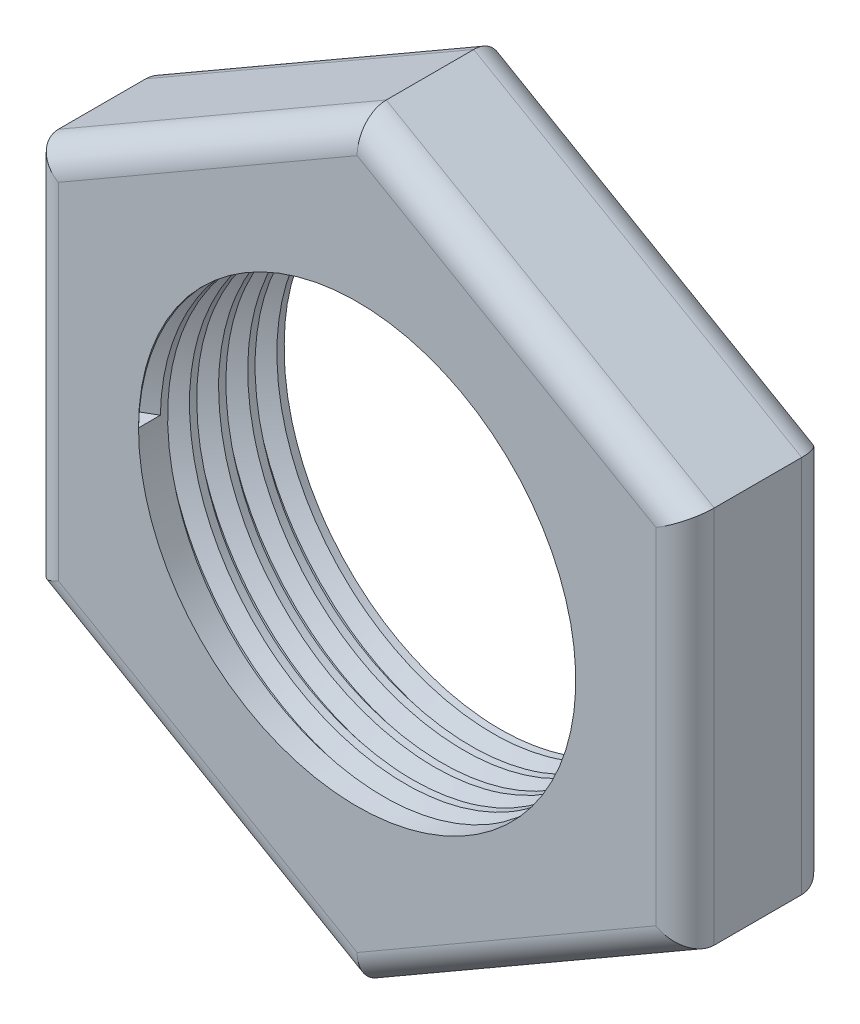
SolidWorks part; units mm, degrees
material "0.6010 (EN-GJL-100)"
ref_plane "Ön Düzlem" through (0, 0, 0) normal (0, 0, 1) x (1, 0, 0)
ref_plane "Üst Düzlem" through (0, 0, 0) normal (0, 1, 0) x (1, 0, 0)
ref_plane "Sağ Düzlem" through (0, 0, 0) normal (1, 0, 0) x (0, 0, -1)
sketch "Çizim1" plane through (0, 0, 0) normal (0, 0, 1) x (1, 0, 0)
  line L0 (0, 25.9808) -> (0, -25.9808) construction
  line L1 (0, 25.9808) -> (-22.5, 12.9904)
  line L2 (-22.5, 12.9904) -> (-22.5, -12.9904)
  line L3 (-22.5, -12.9904) -> (0, -25.9808)
  line L4 (0, -25.9808) -> (22.5, -12.9904)
  line L5 (22.5, -12.9904) -> (22.5, 12.9904)
  line L6 (22.5, 12.9904) -> (0, 25.9808)
  line L7 (-22.5, 0) -> (22.5, 0) construction
  circle A0 centre (0, 0) radius 22.5 construction
  circle A1 centre (0, 0) radius 15
  dimension "D2" = 30
  dimension "D1" = 45
extrude "Yükseklik-Ekstrüzyon1" add sketch "Çizim1" along normal blind 10
thread "Diş2" pitch 2 method cut profile "Diş Profili2" start angle 0, offset 0, length 10, pitch 2, diameter 30
ref_plane "Düzlem2" through (-15, 0, 10) normal (0, -1, 0) x (-1, 0, 0)
sketch "Diş Profili2" plane through (-15, 0, 10) normal (0, -1, 0) x (-1, 0, 0)
  line L0 (0, 0) -> (0, 2) construction
  line L1 (0, 0) -> (1.0825, 0.625)
  line L2 (1.0825, 0.625) -> (1.0825, 0.875)
  line L3 (1.0825, 0.875) -> (0, 1.5)
  line L4 (1.0825, 0.75) -> (0, 0.75) construction
  line L11 (0, 0) -> (0, 1.5)
  point P2 (0, 0)
  dimension "Pitch" = 2
  dimension "Profile_Angle" = 60
  dimension "Profile_Land" = 0.25
  dimension "Profile_Height" = 1.0825
fillet "Radyus1" radius 2 6 edges at (22.5, 0, 10) (11.25, -19.4856, 10) (-11.25, -19.4856, 10) (-22.5, 0, 10) (-11.25, 19.4856, 10) (11.25, 19.4856, 10)
fillet "Radyus3" radius 2 6 edges at (22.5, 0, 0) (11.25, -19.4856, 0) (-11.25, -19.4856, 0) (-22.5, 0, 0) (-11.25, 19.4856, 0) (11.25, 19.4856, 0)
